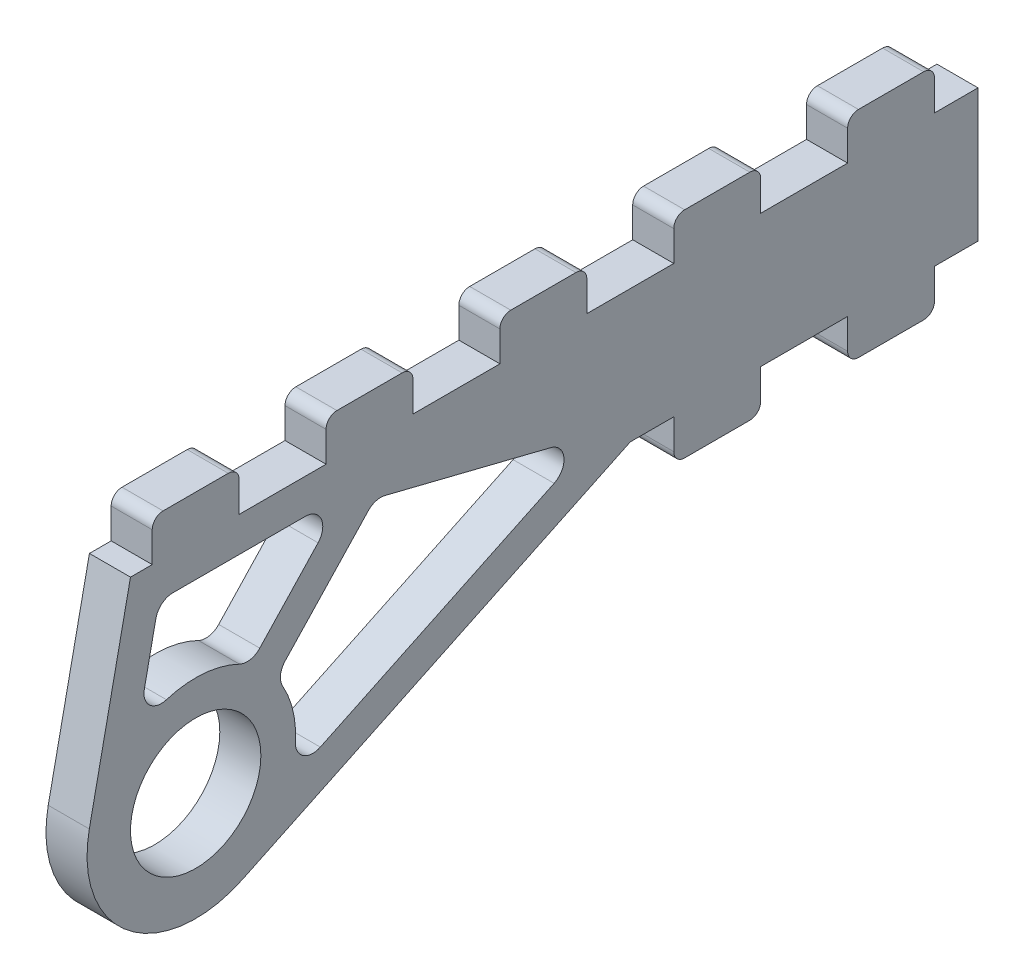
SolidWorks part; units mm, degrees
ref_plane "Front Plane" through (0, 0, 0) normal (0, 0, 1) x (1, 0, 0)
ref_plane "Top Plane" through (0, 0, 0) normal (0, 1, 0) x (1, 0, 0)
ref_plane "Right Plane" through (0, 0, 0) normal (1, 0, 0) x (0, 0, -1)
sketch "Sketch1" plane through (0, 0, 0) normal (1, 0, 0) x (0, 0, -1)
  line L0 (-41.4563, 38.1) -> (38.3452, 38.1) construction
  line L1 (-15.541, 3.2395) -> (-9.525, 32.1)
  line L2 (38.9021, 32.1) -> (-38.9021, 32.1) construction
  line L3 (38.9021, 32.1) -> (38.9021, 38.1) construction
  line L4 (38.9021, 38.1) -> (-38.9021, 38.1) construction
  line L5 (-38.9021, 32.1) -> (-38.9021, 38.1) construction
  line L6 (38.9021, 32.1) -> (-38.9021, 38.1) construction
  line L7 (38.9021, 38.1) -> (-38.9021, 32.1) construction
  line L8 (0, 7.3323) -> (-6.35, 3.6662) construction
  line L9 (-6.35, 3.6662) -> (-6.35, -3.6662) construction
  line L10 (-6.35, -3.6662) -> (0, -7.3323) construction
  line L11 (0, -7.3323) -> (6.35, -3.6662) construction
  line L12 (6.35, -3.6662) -> (6.35, 3.6662) construction
  line L13 (6.35, 3.6662) -> (0, 7.3323) construction
  line L14 (-9.525, 32.1) -> (63.5, 32.1)
  line L15 (0, -15.875) -> (63.5, -15.875)
  line L16 (63.5, -15.875) -> (63.5, 32.1)
  line L18 (157.9971, 6.7) -> (88.9, 6.7) construction
  line L19 (157.9971, 6.7) -> (157.9971, 12.7) construction
  line L20 (157.9971, 12.7) -> (88.9, 12.7) construction
  line L21 (88.9, 6.7) -> (88.9, 12.7) construction
  line L22 (157.9971, 6.7) -> (88.9, 12.7) construction
  line L23 (157.9971, 12.7) -> (88.9, 6.7) construction
  circle A0 centre (0, 0) radius 9.525
  arc A1 (-15.541, 3.2395) -> (0, -15.875) centre (0, 0) ccw
  circle A2 centre (0, 0) radius 25.4 construction
  circle A3 centre (0, 0) radius 6.35 construction
  arc A4 (0, -15.875) -> (-15.541, 3.2395) centre (0, 0) ccw construction
  point P3 (123.4486, 9.7)
  point P7 (0, 35.1)
  point P28 (88.9, 9.7)
  dimension "D1" = 19.05
  dimension "D2" = 6.35
  dimension "D4" = 50.8
  dimension "D3" = 38.1
  dimension "D5" = 6
  dimension "D6" = 12.7
  dimension "D7" = 9.525
  dimension "D8" = 63.5
  dimension "D9" = 25.4
  dimension "D10" = 88.9
extrude "Boss-Extrude1" add sketch "Sketch1" along normal mid plane 6
sketch "Sketch2" plane through (3, 0, 0) normal (1, 0, 0) x (0, 0, -1)
  line L0 (6.8345, -14.3285) -> (63.5, 12.7)
  line L2 (63.5, -15.875) -> (63.5, 32.1) construction
  line L5 (63.5, 12.7) -> (63.5, -15.875)
  line L8 (63.5, -15.875) -> (0, -15.875)
  line L11 (0, -15.875) -> (63.5, -15.875) construction
  line L12 (157.9971, 12.7) -> (88.9, 12.7) construction
  line L22 (0, 0) -> (15.49, 0) construction
  circle A10 centre (0, 0) radius 15.875 construction
  arc A11 (6.8345, -14.3285) -> (0, -15.875) centre (0, 0) cw
  arc A13 (-15.541, 3.2395) -> (0, -15.875) centre (0, 0) ccw construction
  point P12 (0, 0)
extrude "Cut-Extrude1" cut sketch "Sketch2" against normal through all
sketch "Sketch4" plane through (3, 0, 0) normal (1, 0, 0) x (0, 0, -1)
  line L0 (157.9971, 12.7) -> (88.9, 12.7) construction
  line L1 (63.5, 32.1) -> (114.3, 32.1)
  line L2 (63.5, 32.1) -> (63.5, 12.7)
  line L3 (63.5, 12.7) -> (114.3, 12.7)
  line L4 (114.3, 32.1) -> (114.3, 12.7)
  line L5 (88.9, 6.7) -> (88.9, 12.7) construction
  dimension "D1" = 25.4
extrude "Boss-Extrude3" add sketch "Sketch4" against normal up to surface (6 mm away) up to face at (-3, 11.7739, -20.6636)
sketch "Sketch3" plane through (0, 32.1, 0) normal (0, 1, 0) x (1, 0, 0)
  line L0 (3, 114.3) -> (3, -9.525) construction
  line L1 (-3, -6.35) -> (3, -6.35)
  line L2 (-3, -6.35) -> (-3, 6.35)
  line L3 (-3, 6.35) -> (3, 6.35)
  line L4 (3, -6.35) -> (3, 6.35)
  line L5 (-3, -6.35) -> (3, 6.35) construction
  line L6 (-3, 6.35) -> (3, -6.35) construction
  point P0 (0, 0)
  dimension "D1" = 12.7
extrude "Boss-Extrude2" add sketch "Sketch3" along normal blind 6
fillet "Fillet1" radius 1.5875 2 edges at (0, 38.1, -6.35) (0, 38.1, 6.35)
pattern_linear "LPattern1" count 5 spacing 25.4 along (0, 0, -1) of "Boss-Extrude2", "Fillet1"
sketch "Sketch5" plane through (-3, 0, 0) normal (-1, 0, 0) x (0, 0, 1)
  line L0 (-114.3, 12.7) -> (-63.5, 12.7) construction
  line L1 (-69.85, 12.7) -> (-82.55, 12.7)
  line L2 (-69.85, 12.7) -> (-69.85, 6.7)
  line L3 (-69.85, 6.7) -> (-82.55, 6.7)
  line L4 (-82.55, 12.7) -> (-82.55, 6.7)
  line L5 (-69.85, 36.5125) -> (-69.85, 32.1) construction
  line L6 (-82.55, 36.5125) -> (-82.55, 32.1) construction
  dimension "D1" = 6
extrude "Boss-Extrude4" add sketch "Sketch5" against normal up to surface (6 mm away) up to face at (3, 31.7217, -49.7894)
fillet "Fillet2" radius 1.5875 2 edges at (0, 6.7, -69.85) (0, 6.7, -82.55)
pattern_linear "LPattern2" count 2 spacing 25.4 along (0, 0, -1) of "Boss-Extrude4", "Fillet2"
sketch "Sketch6" plane through (3, 0, 0) normal (1, 0, 0) x (0, 0, -1)
  line L0 (-5.3947, 27.02) -> (-10.5678, 2.2029)
  line L1 (4.6474, -9.7434) -> (62.3505, 17.78)
  line L2 (62.3505, 17.78) -> (74.93, 17.78)
  line L3 (74.93, 17.78) -> (74.93, 11.78)
  line L4 (74.93, 11.78) -> (77.47, 11.78)
  line L5 (77.47, 11.78) -> (77.47, 17.78)
  line L6 (77.47, 17.78) -> (100.33, 17.78)
  line L7 (100.33, 17.78) -> (100.33, 11.78)
  line L8 (100.33, 11.78) -> (102.87, 11.78)
  line L9 (102.87, 11.78) -> (102.87, 17.78)
  line L10 (102.87, 17.78) -> (109.22, 17.78)
  line L11 (109.22, 17.78) -> (109.22, 27.02)
  line L12 (109.22, 27.02) -> (102.87, 27.02)
  line L13 (102.87, 27.02) -> (102.87, 33.02)
  line L14 (102.87, 33.02) -> (100.33, 33.02)
  line L15 (100.33, 33.02) -> (100.33, 27.02)
  line L16 (100.33, 27.02) -> (77.47, 27.02)
  line L17 (77.47, 27.02) -> (77.47, 33.02)
  line L18 (77.47, 33.02) -> (74.93, 33.02)
  line L19 (74.93, 33.02) -> (74.93, 27.02)
  line L20 (74.93, 27.02) -> (52.07, 27.02)
  line L21 (52.07, 27.02) -> (52.07, 33.02)
  line L22 (52.07, 33.02) -> (49.53, 33.02)
  line L23 (49.53, 33.02) -> (49.53, 27.02)
  line L24 (49.53, 27.02) -> (26.67, 27.02)
  line L25 (26.67, 27.02) -> (26.67, 33.02)
  line L26 (26.67, 33.02) -> (24.13, 33.02)
  line L27 (24.13, 33.02) -> (24.13, 27.02)
  line L28 (24.13, 27.02) -> (1.27, 27.02)
  line L29 (1.27, 27.02) -> (1.27, 33.02)
  line L30 (1.27, 33.02) -> (-1.27, 33.02)
  line L31 (-1.27, 33.02) -> (-1.27, 27.02)
  line L32 (-1.27, 27.02) -> (-5.3947, 27.02)
  line L33 (95.25, 12.7) -> (95.25, 8.2875)
  line L34 (96.8375, 6.7) -> (106.3625, 6.7)
  line L35 (107.95, 8.2875) -> (107.95, 12.7)
  line L36 (107.95, 12.7) -> (114.3, 12.7)
  line L37 (114.3, 12.7) -> (114.3, 32.1)
  line L38 (114.3, 32.1) -> (107.95, 32.1)
  line L39 (107.95, 32.1) -> (107.95, 36.5125)
  line L40 (106.3625, 38.1) -> (96.8375, 38.1)
  line L41 (95.25, 36.5125) -> (95.25, 32.1)
  line L42 (95.25, 32.1) -> (82.55, 32.1)
  line L43 (82.55, 32.1) -> (82.55, 36.5125)
  line L44 (80.9625, 38.1) -> (71.4375, 38.1)
  line L45 (69.85, 36.5125) -> (69.85, 32.1)
  line L46 (69.85, 32.1) -> (57.15, 32.1)
  line L47 (57.15, 32.1) -> (57.15, 36.5125)
  line L48 (55.5625, 38.1) -> (46.0375, 38.1)
  line L49 (44.45, 36.5125) -> (44.45, 32.1)
  line L50 (44.45, 32.1) -> (31.75, 32.1)
  line L51 (31.75, 32.1) -> (31.75, 36.5125)
  line L52 (30.1625, 38.1) -> (20.6375, 38.1)
  line L53 (19.05, 36.5125) -> (19.05, 32.1)
  line L54 (19.05, 32.1) -> (6.35, 32.1)
  line L55 (6.35, 32.1) -> (6.35, 36.5125)
  line L56 (4.7625, 38.1) -> (-4.7625, 38.1)
  line L57 (-6.35, 36.5125) -> (-6.35, 32.1)
  line L58 (-6.35, 32.1) -> (-9.525, 32.1)
  line L59 (-9.525, 32.1) -> (-15.541, 3.2395)
  line L60 (6.8345, -14.3285) -> (63.5, 12.7)
  line L61 (63.5, 12.7) -> (69.85, 12.7)
  line L62 (69.85, 12.7) -> (69.85, 8.2875)
  line L63 (71.4375, 6.7) -> (80.9625, 6.7)
  line L64 (82.55, 8.2875) -> (82.55, 12.7)
  line L65 (82.55, 12.7) -> (95.25, 12.7)
  line L66 (95.25, 12.7) -> (95.25, 8.2875)
  line L67 (96.8375, 6.7) -> (106.3625, 6.7)
  line L68 (107.95, 8.2875) -> (107.95, 12.7)
  line L69 (107.95, 12.7) -> (114.3, 12.7)
  line L70 (114.3, 12.7) -> (114.3, 32.1)
  line L71 (114.3, 32.1) -> (107.95, 32.1)
  line L72 (107.95, 32.1) -> (107.95, 36.5125)
  line L73 (106.3625, 38.1) -> (96.8375, 38.1)
  line L74 (95.25, 36.5125) -> (95.25, 32.1)
  line L75 (95.25, 32.1) -> (82.55, 32.1)
  line L76 (82.55, 32.1) -> (82.55, 36.5125)
  line L77 (80.9625, 38.1) -> (71.4375, 38.1)
  line L78 (69.85, 36.5125) -> (69.85, 32.1)
  line L79 (69.85, 32.1) -> (57.15, 32.1)
  line L80 (57.15, 32.1) -> (57.15, 36.5125)
  line L81 (55.5625, 38.1) -> (46.0375, 38.1)
  line L82 (44.45, 36.5125) -> (44.45, 32.1)
  line L83 (44.45, 32.1) -> (31.75, 32.1)
  line L84 (31.75, 32.1) -> (31.75, 36.5125)
  line L85 (30.1625, 38.1) -> (20.6375, 38.1)
  line L86 (19.05, 36.5125) -> (19.05, 32.1)
  line L87 (19.05, 32.1) -> (6.35, 32.1)
  line L88 (6.35, 32.1) -> (6.35, 36.5125)
  line L89 (4.7625, 38.1) -> (-4.7625, 38.1)
  line L90 (-6.35, 36.5125) -> (-6.35, 32.1)
  line L91 (-6.35, 32.1) -> (-9.525, 32.1)
  line L92 (-9.525, 32.1) -> (-15.541, 3.2395)
  line L93 (6.8345, -14.3285) -> (63.5, 12.7)
  line L94 (63.5, 12.7) -> (69.85, 12.7)
  line L95 (69.85, 12.7) -> (69.85, 8.2875)
  line L96 (71.4375, 6.7) -> (80.9625, 6.7)
  line L97 (82.55, 8.2875) -> (82.55, 12.7)
  line L98 (82.55, 12.7) -> (95.25, 12.7)
  line L99 (0, 0) -> (25.3883, 27.02) construction
  line L100 (25.3883, 27.02) -> (62.3505, 17.78) construction
  line L101 (1.8511, -1.7393) -> (26.2186, 24.1943)
  line L102 (26.2186, 24.1943) -> (61.7345, 15.3158)
  line L103 (-1.8511, 1.7393) -> (24.5581, 29.8457)
  line L104 (24.5581, 29.8457) -> (62.9665, 20.2442)
  line L105 (-1.27, 27.02) -> (1.27, 27.02)
  circle A0 centre (0, 0) radius 9.525 construction
  circle A1 centre (0, 0) radius 9.525
  arc A2 (-10.5678, 2.2029) -> (4.6474, -9.7434) centre (0, 0) ccw
  arc A3 (74.93, 11.78) -> (74.93, 11.78) centre (74.93, 11.78) ccw
  arc A4 (77.47, 11.78) -> (77.47, 11.78) centre (77.47, 11.78) ccw
  arc A5 (100.33, 11.78) -> (100.33, 11.78) centre (100.33, 11.78) ccw
  arc A6 (102.87, 11.78) -> (102.87, 11.78) centre (102.87, 11.78) ccw
  arc A7 (102.87, 33.02) -> (102.87, 33.02) centre (102.87, 33.02) ccw
  arc A8 (100.33, 33.02) -> (100.33, 33.02) centre (100.33, 33.02) ccw
  arc A9 (77.47, 33.02) -> (77.47, 33.02) centre (77.47, 33.02) ccw
  arc A10 (74.93, 33.02) -> (74.93, 33.02) centre (74.93, 33.02) ccw
  arc A11 (52.07, 33.02) -> (52.07, 33.02) centre (52.07, 33.02) ccw
  arc A12 (49.53, 33.02) -> (49.53, 33.02) centre (49.53, 33.02) ccw
  arc A13 (26.67, 33.02) -> (26.67, 33.02) centre (26.67, 33.02) ccw
  arc A14 (24.13, 33.02) -> (24.13, 33.02) centre (24.13, 33.02) ccw
  arc A15 (95.25, 8.2875) -> (96.8375, 6.7) centre (96.8375, 8.2875) ccw
  arc A16 (106.3625, 6.7) -> (107.95, 8.2875) centre (106.3625, 8.2875) ccw
  arc A17 (107.95, 36.5125) -> (106.3625, 38.1) centre (106.3625, 36.5125) ccw
  arc A18 (96.8375, 38.1) -> (95.25, 36.5125) centre (96.8375, 36.5125) ccw
  arc A19 (82.55, 36.5125) -> (80.9625, 38.1) centre (80.9625, 36.5125) ccw
  arc A20 (71.4375, 38.1) -> (69.85, 36.5125) centre (71.4375, 36.5125) ccw
  arc A21 (57.15, 36.5125) -> (55.5625, 38.1) centre (55.5625, 36.5125) ccw
  arc A22 (46.0375, 38.1) -> (44.45, 36.5125) centre (46.0375, 36.5125) ccw
  arc A23 (31.75, 36.5125) -> (30.1625, 38.1) centre (30.1625, 36.5125) ccw
  arc A24 (20.6375, 38.1) -> (19.05, 36.5125) centre (20.6375, 36.5125) ccw
  arc A25 (6.35, 36.5125) -> (4.7625, 38.1) centre (4.7625, 36.5125) ccw
  arc A26 (-4.7625, 38.1) -> (-6.35, 36.5125) centre (-4.7625, 36.5125) ccw
  arc A27 (-15.541, 3.2395) -> (6.8345, -14.3285) centre (0, 0) ccw
  arc A28 (69.85, 8.2875) -> (71.4375, 6.7) centre (71.4375, 8.2875) ccw
  arc A29 (80.9625, 6.7) -> (82.55, 8.2875) centre (80.9625, 8.2875) ccw
  arc A30 (95.25, 8.2875) -> (96.8375, 6.7) centre (96.8375, 8.2875) ccw
  arc A31 (106.3625, 6.7) -> (107.95, 8.2875) centre (106.3625, 8.2875) ccw
  arc A32 (107.95, 36.5125) -> (106.3625, 38.1) centre (106.3625, 36.5125) ccw
  arc A33 (96.8375, 38.1) -> (95.25, 36.5125) centre (96.8375, 36.5125) ccw
  arc A34 (82.55, 36.5125) -> (80.9625, 38.1) centre (80.9625, 36.5125) ccw
  arc A35 (71.4375, 38.1) -> (69.85, 36.5125) centre (71.4375, 36.5125) ccw
  arc A36 (57.15, 36.5125) -> (55.5625, 38.1) centre (55.5625, 36.5125) ccw
  arc A37 (46.0375, 38.1) -> (44.45, 36.5125) centre (46.0375, 36.5125) ccw
  arc A38 (31.75, 36.5125) -> (30.1625, 38.1) centre (30.1625, 36.5125) ccw
  arc A39 (20.6375, 38.1) -> (19.05, 36.5125) centre (20.6375, 36.5125) ccw
  arc A40 (6.35, 36.5125) -> (4.7625, 38.1) centre (4.7625, 36.5125) ccw
  arc A41 (-4.7625, 38.1) -> (-6.35, 36.5125) centre (-4.7625, 36.5125) ccw
  arc A42 (-15.541, 3.2395) -> (6.8345, -14.3285) centre (0, 0) ccw
  arc A43 (69.85, 8.2875) -> (71.4375, 6.7) centre (71.4375, 8.2875) ccw
  arc A44 (80.9625, 6.7) -> (82.55, 8.2875) centre (80.9625, 8.2875) ccw
  arc A45 (1.27, 33.02) -> (1.27, 33.02) centre (1.27, 33.02) ccw
  arc A46 (-1.27, 33.02) -> (-1.27, 33.02) centre (-1.27, 33.02) ccw
  circle A47 centre (0, 0) radius 14.605
  dimension "D1" = 0
  dimension "D2" = 5.08
  dimension "D3" = 5.08
  dimension "D4" = 2.54
  dimension "D5" = 2.54
extrude "Cut-Extrude2" cut sketch "Sketch6" against normal through all contours A47 L103 L28 L105 L32 L0 | A47 L1 L102 L101 region at (3, 20.8392, -4.7306) region at (3, 11.4157, -30.486)
fillet "Fillet3" radius 2.54 8 edges at (0, 8.7422, -11.6996) (0, 24.1943, -26.2186) (0, 16.0622, -58.749) (0, 11.8332, 8.5604) (0, 27.02, 5.3947) (0, 27.02, -21.903) (0, 12.2208, -7.9974) (0, -5.5082, -13.5265)
